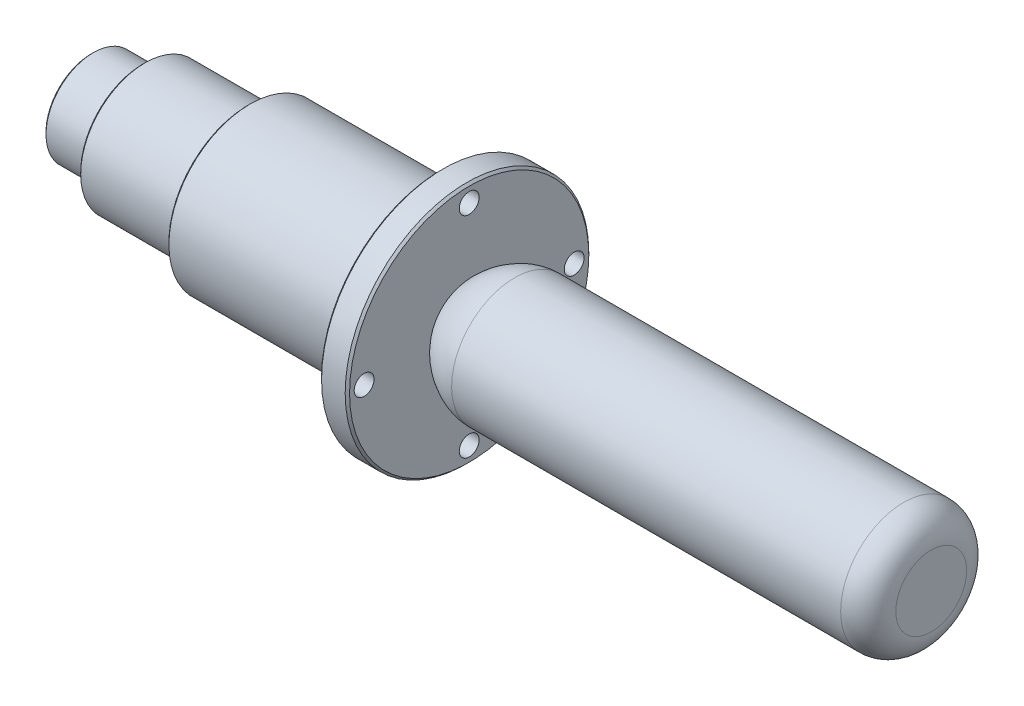
SolidWorks part; units mm, degrees
ref_plane "Front Plane" through (0, 0, 0) normal (0, 0, 1) x (1, 0, 0)
ref_plane "Top Plane" through (0, 0, 0) normal (0, 1, 0) x (1, 0, 0)
ref_plane "Right Plane" through (0, 0, 0) normal (1, 0, 0) x (0, 0, -1)
sketch "Sketch1" plane through (0, 0, 0) normal (0, 0, 1) x (1, 0, 0)
  line L0 (-19.6703, 0) -> (-19.6703, 8.5806)
  line L1 (-19.6703, 8.5806) -> (-10.2723, 8.5806)
  line L2 (-10.2723, 8.5806) -> (-10.2723, 11.684)
  line L3 (-10.2723, 11.684) -> (8.7777, 11.684)
  line L4 (8.7777, 11.684) -> (8.7777, 14.732)
  line L5 (8.7777, 14.732) -> (43.8297, 14.732)
  line L6 (43.8297, 14.732) -> (43.8297, 22.098)
  line L7 (43.8297, 22.098) -> (48.9097, 22.098)
  line L8 (48.9097, 22.098) -> (48.9097, 7.0552)
  line L9 (57.156, 11.43) -> (127.7297, 11.43)
  line L10 (-19.6703, 0) -> (132.7297, 0)
  line L11 (132.7297, 0) -> (132.7297, 6.43)
  arc A0 (127.7297, 11.43) -> (132.7297, 6.43) centre (127.7297, 6.43) cw
  spline S0 degree 3 poles (48.9097, 7.0552) (50.7457, 9.4694) (54.0783, 11.43) (57.156, 11.43) knots 0 0 0 0 1 1 1 1
  point P17 (92.4428, 11.43)
  dimension "D1" = 5
  dimension "D2" = 11.43
  dimension "D3" = 11.684
  dimension "D4" = 14.732
  dimension "D5" = 22.098
  dimension "D6" = 5.08
  dimension "D7" = 35.052
  dimension "D8" = 68.58
  dimension "D9" = 152.4
  dimension "D10" = 19.05
revolve "Revolve1" add sketch "Sketch1" angle 360 about L10
sketch "Sketch2" plane through (48.9097, 0, 0) normal (1, 0, 0) x (0, 0, -1)
  circle A0 centre (0, 0) radius 19.05 construction
  circle A1 centre (0, 19.05) radius 1.8034
  dimension "D1" = 38.1
extrude "Cut-Extrude1" cut sketch "Sketch2" against normal up to next
pattern_circular "CirPattern2" count 4 over 360 about axis through (48.9097, 0, 0) along (-1, 0, 0) of "Cut-Extrude1"
chamfer "Chamfer1" distance 0.3969 angle 45 5 edges at (48.9097, 0, 22.098) (43.8297, 0, 22.098) (8.7777, 0, 14.732) (-10.2723, 0, 11.684) (-19.6703, 0, 8.5806)
equation "\"D3@Sketch1\"=0.92/2"
equation "\"D4@Sketch1\"=1.16/2"
